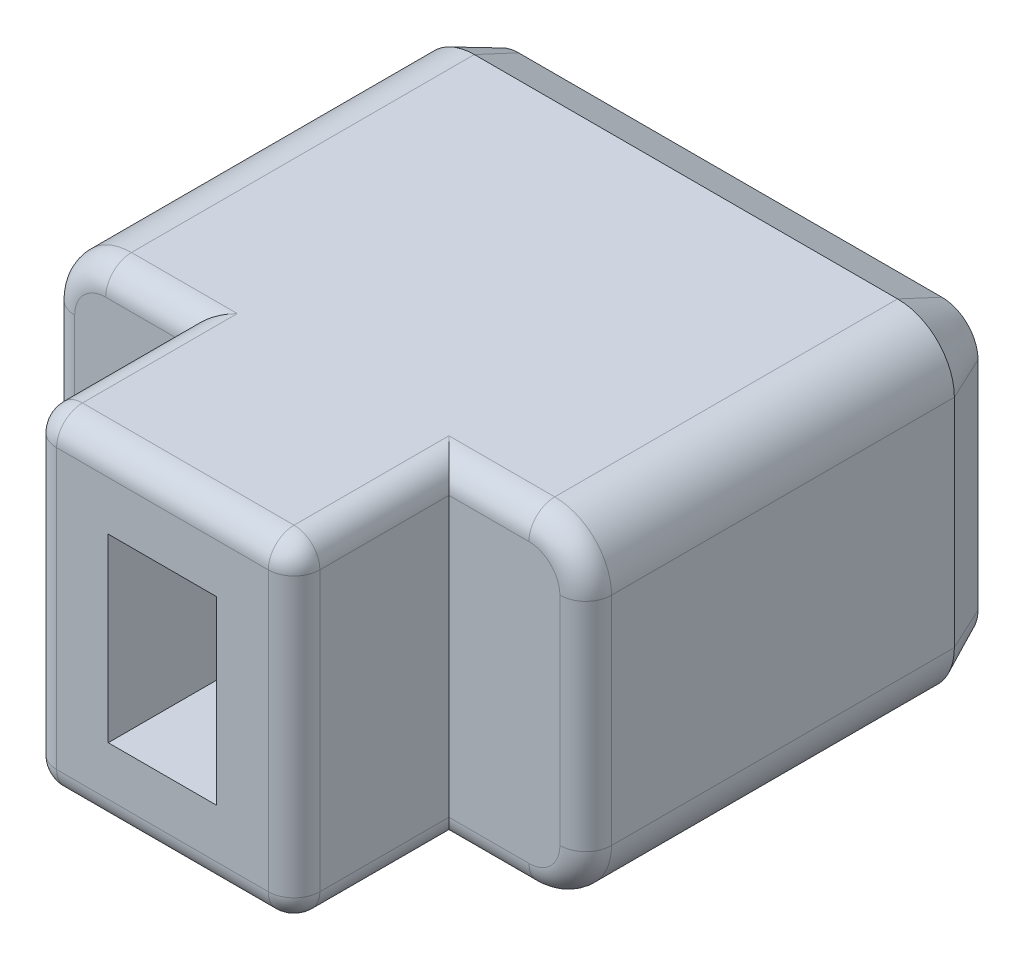
SolidWorks part; units mm, degrees
ref_plane "Plan de face" through (0, 0, 0) normal (0, 0, 1) x (1, 0, 0)
ref_plane "Plan de dessus" through (0, 0, 0) normal (0, 1, 0) x (1, 0, 0)
ref_plane "Plan de droite" through (0, 0, 0) normal (1, 0, 0) x (0, 0, -1)
sketch "Esquisse2" plane through (0, 0, 0) normal (0, 0, 1) x (1, 0, 0)
  line L1 (1.1, 0) -> (9.3, 0)
  line L2 (0, 1.1) -> (0, 5.3)
  line L3 (1.1, 6.4) -> (9.3, 6.4)
  line L4 (10.4, 1.1) -> (10.4, 5.3)
  arc A0 (9.3, 6.4) -> (10.4, 5.3) centre (9.3, 5.3) cw
  arc A1 (9.3, 0) -> (10.4, 1.1) centre (9.3, 1.1) ccw
  arc A2 (1.1, 0) -> (0, 1.1) centre (1.1, 1.1) cw
  arc A3 (0, 5.3) -> (1.1, 6.4) centre (1.1, 5.3) cw
  point P7 (10.4, 6.4)
  point P12 (0, 0)
  point P15 (0, 6.4)
  dimension "D3" = 1.1
  dimension "D1" = 10.4
  dimension "D2" = 6.4
extrude "Boss.-Extru.1" add sketch "Esquisse2" along normal blind 11
sketch "Esquisse3" plane through (0, 0, 11) normal (0, 0, 1) x (1, 0, 0)
  line L0 (0, 5.3) -> (0, 1.1) construction
  line L1 (4.15, 4.95) -> (6.25, 4.95)
  line L2 (4.15, 4.95) -> (4.15, 1.45)
  line L3 (4.15, 1.45) -> (6.25, 1.45)
  line L4 (6.25, 4.95) -> (6.25, 1.45)
  line L5 (10.4, 1.1) -> (10.4, 5.3) construction
  line L6 (9.3, 6.4) -> (1.1, 6.4) construction
  line L7 (1.1, 0) -> (9.3, 0) construction
  dimension "D1" = 2.1
  dimension "D2" = 3.5
  dimension "D3" = 4.15
  dimension "D4" = 4.15
  dimension "D5" = 1.45
  dimension "D6" = 1.45
extrude "Enlèv. mat.-Extru.1" cut sketch "Esquisse3" against normal blind 3
sketch "Esquisse4" plane through (0, 0, 11) normal (0, 0, 1) x (1, 0, 0)
  line L0 (2.65, 6.4) -> (2.65, 0)
  line L1 (9.3, 6.4) -> (1.1, 6.4) construction
  line L2 (1.1, 0) -> (9.3, 0) construction
  line L3 (2.65, 0) -> (7.75, 0)
  line L4 (7.75, 0) -> (7.75, 6.4)
  line L5 (7.75, 6.4) -> (2.65, 6.4)
  line L6 (4.15, 4.95) -> (4.15, 1.45) construction
  line L7 (6.25, 1.45) -> (6.25, 4.95) construction
  dimension "D1" = 1.5
  dimension "D2" = 1.5
extrude "Enlèv. mat.-Extru.2" cut sketch "Esquisse4" against normal blind 3 flip side to cut
fillet "Congé1" radius 0.5 18 edges at (8.525, 0, 8) (10.0778, 0.3222, 8) (10.4, 3.2, 8) (10.0778, 6.0778, 8) (1.875, 6.4, 8) (0.3222, 6.0778, 8) (1.875, 0, 8) (0.3222, 0.3222, 8) (7.75, 6.4, 9.5) (2.65, 6.4, 9.5) (7.75, 0, 9.5) (2.65, 0, 9.5) (2.65, 3.2, 11) (5.2, 6.4, 11) (7.75, 3.2, 11) (5.2, 0, 11) (8.525, 6.4, 8) (0, 3.2, 8)
chamfer "Chanfrein1" distance 0.4 angle 65 8 edges at (5.2, 0, 0) (10.0778, 0.3222, 0) (0.3222, 0.3222, 0) (10.4, 3.2, 0) (0, 3.2, 0) (10.0778, 6.0778, 0) (0.3222, 6.0778, 0) (5.2, 6.4, 0) first distance on face at (5.2, 3.2, 0)
sketch "Esquisse5" plane through (0, 0, 0) normal (0, 0, -1) x (-1, 0, 0)
  line L0 (-0.4, 5.3) -> (-10, 5.3) construction
  arc A0 (-9.3, 6) -> (-10, 5.3) centre (-9.3, 5.3) ccw construction
  text T0 "IDT" font "Century Gothic" height 4.1
extrude "Enlèv. mat.-Extru.3" cut sketch "Esquisse5" against normal blind 0.3
extrude "Boss.-Extru.2" add sketch "Esquisse5<2>" along normal blind 0.3 separate body
sketch "Esquisse5<2>" plane through (0, 0, 0) normal (0, 0, -1) x (-1, 0, 0) same geometry as "Esquisse5"
